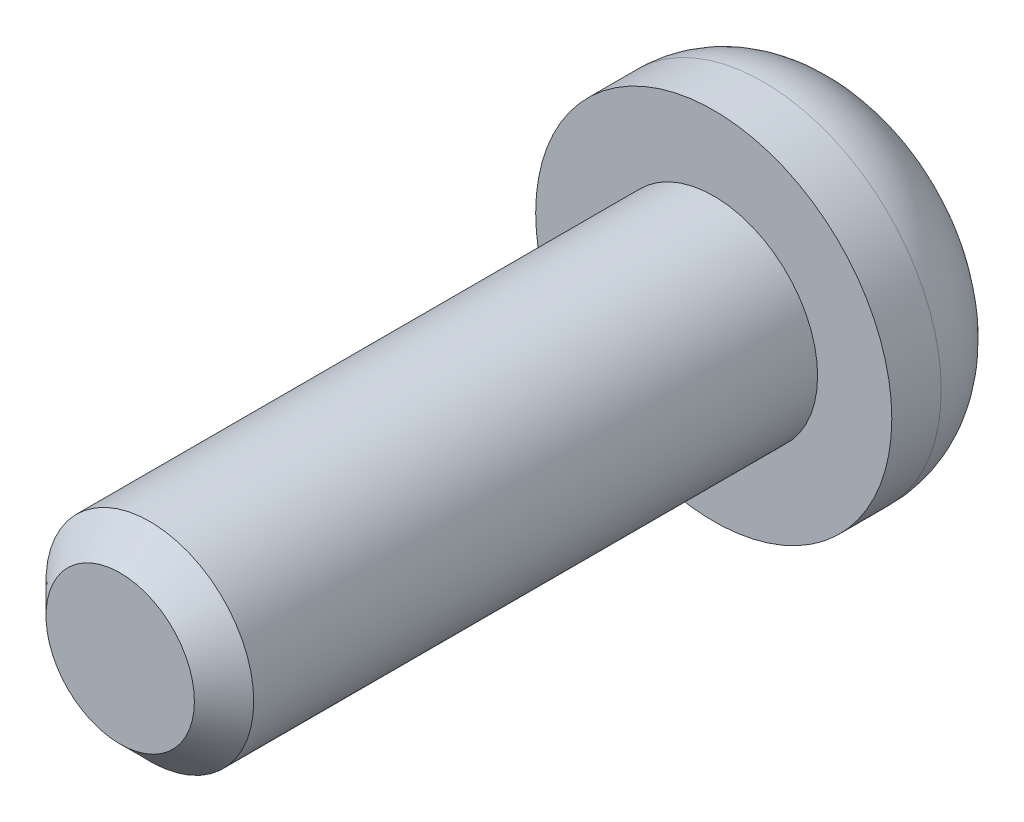
SolidWorks part; units mm, degrees
ref_plane "Přední rovina" through (0, 0, 0) normal (0, 0, 1) x (1, 0, 0)
ref_plane "Horní rovina" through (0, 0, 0) normal (0, 1, 0) x (1, 0, 0)
ref_plane "Pravá rovina" through (0, 0, 0) normal (1, 0, 0) x (0, 0, -1)
sketch "Skica1" plane through (0, 0, 0) normal (0, 0, 1) x (1, 0, 0)
  circle A0 centre (0, 0) radius 1.8
  dimension "D1" = 3.6
extrude "Přidat vysunutím1" add sketch "Skica1" along normal blind 1.4
sketch "Skica2" plane through (0, 0, 0) normal (0, 0, -1) x (-1, 0, 0)
  line L0 (-1.8, 0) -> (1.8, 0) construction
  line L1 (-0.4435, 0.4117) -> (-1.2442, 0.4117)
  line L2 (0.4435, 0.4117) -> (1.2442, 0.4117)
  line L3 (-1.2442, 0.4117) -> (-1.2442, -0.4117)
  line L4 (-0.4435, 0.4117) -> (-0.4435, 1.3889)
  line L5 (-0.4435, -0.4117) -> (-0.4435, -1.3889)
  line L6 (-0.4435, 1.3889) -> (0, 1.3889)
  line L7 (-0.4435, -1.3889) -> (0, -1.3889)
  line L8 (0.4435, 0.4117) -> (0.4435, 1.3889)
  line L9 (0.4435, -0.4117) -> (0.4435, -1.3889)
  line L10 (0, 1.8) -> (0, -1.8) construction
  line L11 (1.2442, 0.4117) -> (1.2442, -0.4117)
  line L12 (-1.2442, -0.4117) -> (-0.4435, -0.4117)
  line L13 (1.2442, -0.4117) -> (0.4435, -0.4117)
  line L14 (0.4435, 1.3889) -> (0, 1.3889)
  line L15 (0.4435, -1.3889) -> (0, -1.3889)
  circle A0 centre (0, 0) radius 1.8 construction
  point P8 (1.183, 0)
  point P18 (-1.3627, 0)
extrude "Odebrat vysunutím1" cut sketch "Skica2" against normal blind 0.8
sketch "Skica4" plane through (0, 0, 1.4) normal (0, 0, 1) x (1, 0, 0)
  circle A0 centre (0, 0) radius 1.05
  dimension "D1" = 2.1
extrude "Přidat vysunutím2" add sketch "Skica4" along normal blind 6
chamfer "Zkosení1" distance 0.3 angle 45 1 edges at (1.05, 0, 7.4)
fillet "Zaoblit1" radius 0.9 1 edges at (1.8, 0, 0)
